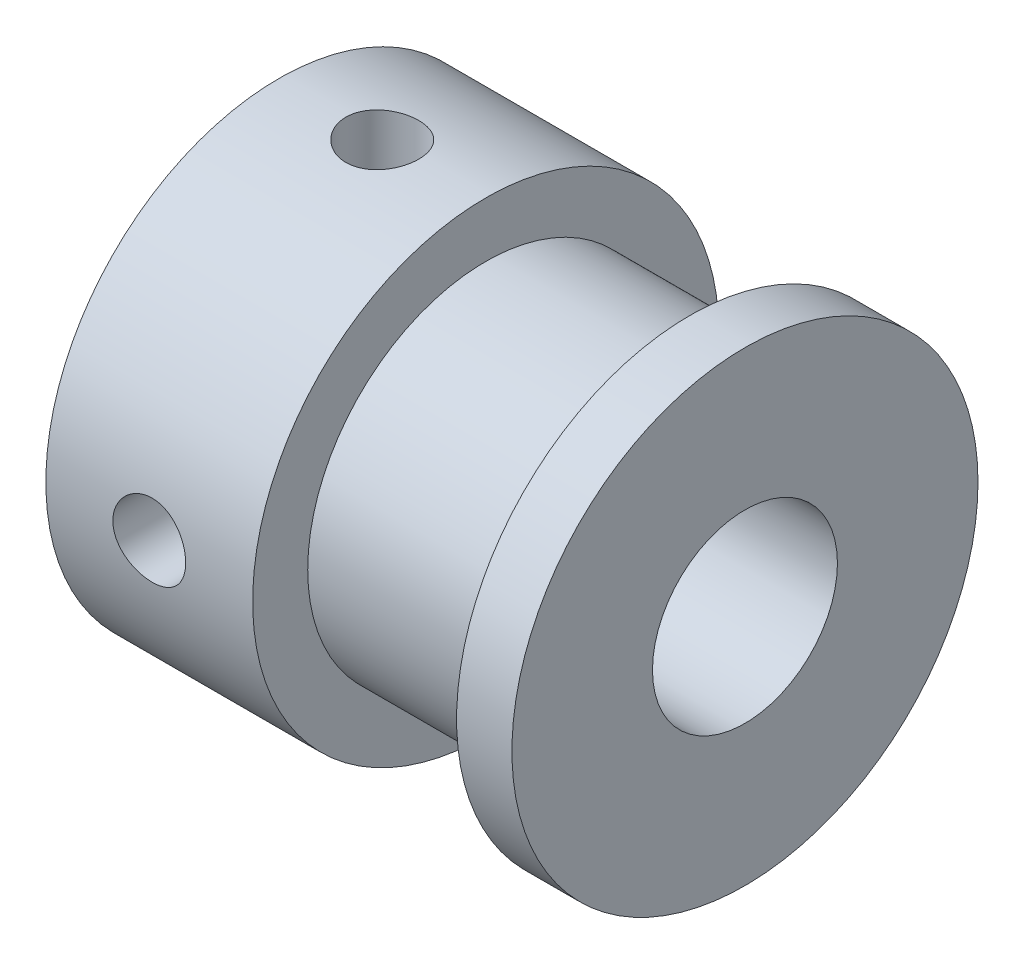
SolidWorks part; units mm, degrees
material "6061-T6 (SS)"
ref_plane "Front Plane" through (0, 0, 0) normal (0, 0, 1) x (1, 0, 0)
ref_plane "Top Plane" through (0, 0, 0) normal (0, 1, 0) x (1, 0, 0)
ref_plane "Right Plane" through (0, 0, 0) normal (1, 0, 0) x (0, 0, -1)
sketch "Sketch1" plane through (0, 0, 0) normal (0, 0, 1) x (1, 0, 0)
  line L0 (0, 3.175) -> (0, 8)
  line L1 (0, 8) -> (7.1, 8)
  line L2 (7.1, 8) -> (7.1, 6.11)
  line L3 (7.1, 6.11) -> (14.1, 6.11)
  line L4 (14.1, 6.11) -> (14.1, 8)
  line L5 (14.1, 8) -> (16, 8)
  line L6 (16, 8) -> (16, 3.175)
  line L7 (16, 3.175) -> (0, 3.175)
  line L8 (0, 0) -> (-7.6744, 0) construction
  dimension "D1" = 6.35
  dimension "D2" = 16
  dimension "D3" = 12.22
  dimension "D4" = 7.1
  dimension "D5" = 16
  dimension "D6" = 1.9
revolve "Revolve1" add sketch "Sketch1" angle 360 about L8
hole_wizard "M3x0.5 Tapped Hole1" positions "Sketch3" profile "Sketch2" tap size "M3x0.5" standard "ANSI Metric" end condition through all
sketch "Sketch3" plane through (0, 0, 0) normal (0, 1, 0) x (1, 0, 0)
  line L0 (0, 0) -> (7.1, 0) construction
  line L1 (7.1, -6.11) -> (7.1, 6.11) construction
  point P8 (3.55, 0)
sketch "Sketch2" plane through (3.55, 0, 0) normal (1, 0, 0) x (0, 0, -1)
  line L0 (0, 0) -> (0, 8)
  line L1 (0, 8) -> (1.25, 8)
  line L2 (1.25, 8) -> (1.25, 0)
  line L5 (1.25, 0) -> (0, 0)
  line L11 (0, -6.35) -> (0, 107.95) construction
  dimension "Thread Major Dia." = 2.5
  dimension "Thru Tap Drill Depth" = 8
hole_wizard "M3x0.5 Tapped Hole2" positions "Sketch5" profile "Sketch4" tap size "M3x0.5" standard "ANSI Metric" end condition through all
sketch "Sketch5" plane through (0, 0, 0) normal (0, 0, 1) x (1, 0, 0)
  line L0 (0, 0) -> (7.1, 0) construction
  line L1 (7.1, -6.11) -> (7.1, 6.11) construction
  point P7 (3.55, 0)
sketch "Sketch4" plane through (3.55, 0, 0) normal (1, 0, 0) x (0, 1, 0)
  line L0 (0, 0) -> (0, 8)
  line L1 (0, 8) -> (1.25, 8)
  line L2 (1.25, 8) -> (1.25, 0)
  line L5 (1.25, 0) -> (0, 0)
  line L11 (0, -6.35) -> (0, 107.95) construction
  dimension "Thread Major Dia." = 2.5
  dimension "Thru Tap Drill Depth" = 8
